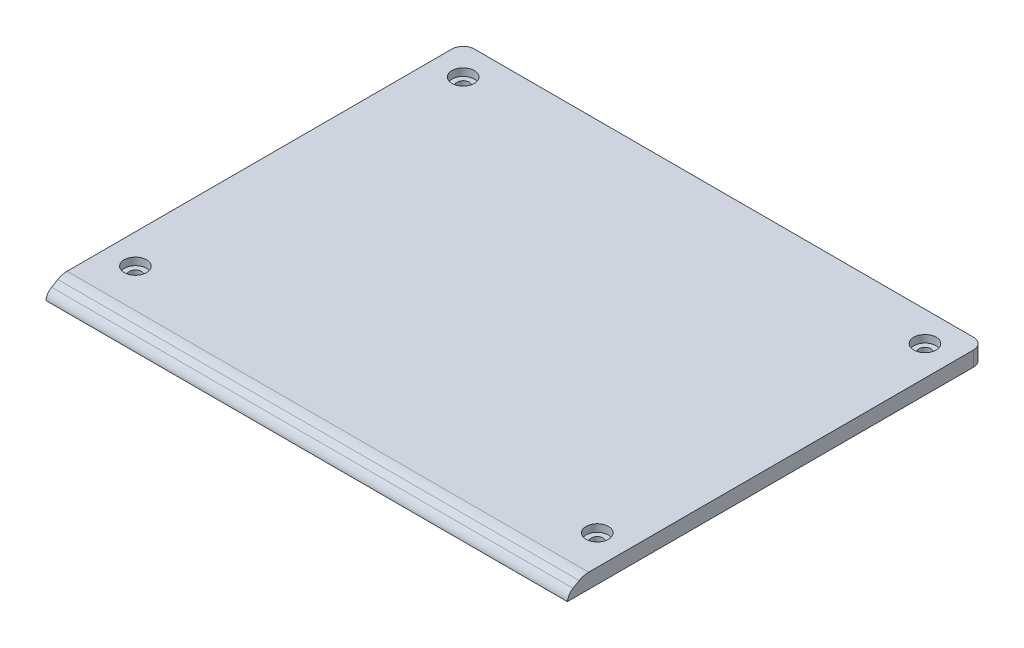
SolidWorks part; units mm, degrees
ref_plane "Спереди XY" through (0, 0, 0) normal (0, 0, 1) x (1, 0, 0)
ref_plane "Сверху XZ" through (0, 0, 0) normal (0, 1, 0) x (1, 0, 0)
ref_plane "Справа ZY" through (0, 0, 0) normal (1, 0, 0) x (0, 0, -1)
sketch "Эскиз1" plane through (0, 0, 0) normal (0, 1, 0) x (1, 0, 0)
  line L1 (-70, 56) -> (70, 56)
  line L2 (-70, 56) -> (-70, -56)
  line L3 (-70, -56) -> (70, -56)
  line L4 (70, 56) -> (70, -56)
  line L5 (-70, 56) -> (70, -56) construction
  line L6 (-70, -56) -> (70, 56) construction
  point P0 (0, 0)
  dimension "D1" = 140
  dimension "D2" = 112
extrude "Бобышка-Вытянуть1" add sketch "Эскиз1" along normal blind 4
chamfer "Фаска1" distance 2.5 angle 60 1 edges at (0, 4, 56) first distance on face at (0, 2, 56)
fillet "Скругление1" radius 5 1 edges at (0, 4, 51.6699)
fillet "Скругление2" radius 3 1 edges at (0, 1.5, 56)
sketch "Эскиз2" plane through (0, 0, 0) normal (0, -1, 0) x (1, 0, 0)
  line L0 (70, 56) -> (70, -56) construction
  line L4 (70, -56) -> (-70, -56) construction
  line L5 (-70, -56) -> (-70, 56) construction
  circle A0 centre (62, -48) radius 1.6
  circle A1 centre (-62, -48) radius 1.6
  circle A2 centre (-62, 40) radius 1.6
  circle A3 centre (62, 40) radius 1.6
  dimension "D1" = 3.2
  dimension "D2" = 8
  dimension "D3" = 8
  dimension "D6" = 8
  dimension "D7" = 8
  dimension "D8" = 8
  dimension "D9" = 8
  dimension "D4" = 2
  dimension "D5" = 2
extrude "Вырез-Вытянуть1" cut sketch "Эскиз2" against normal through all
sketch "Эскиз3" plane through (0, 4, 0) normal (0, 1, 0) x (1, 0, 0)
  circle A0 centre (-62, 48) radius 3
  dimension "D1" = 6
extrude "Вырез-Вытянуть2" cut sketch "Эскиз3" against normal blind 2
pattern_linear "Линейный массив2" count 2 spacing 124 along (1, 0, 0) count 2 spacing 88 along (0, 0, 1) of "Вырез-Вытянуть2"
fillet "Скругление3" radius 3 2 edges at (-70, 2, -56) (70, 2, -56)
